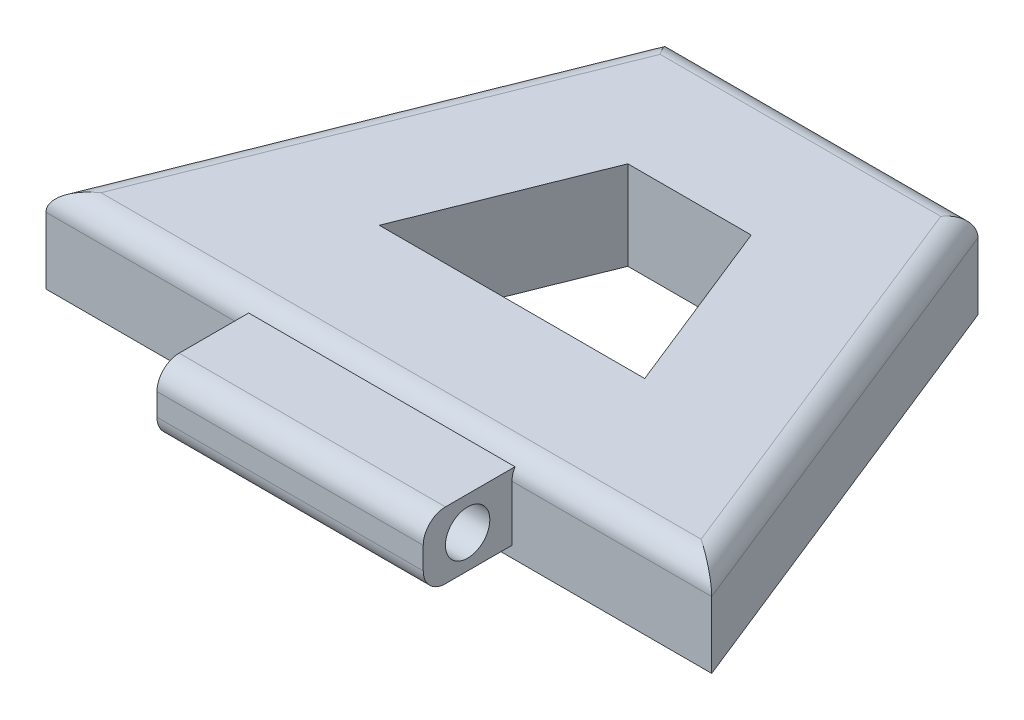
SolidWorks part; units mm, degrees
ref_plane "Front Plane" through (0, 0, 0) normal (0, 0, 1) x (1, 0, 0)
ref_plane "Top Plane" through (0, 0, 0) normal (0, 1, 0) x (1, 0, 0)
ref_plane "Right Plane" through (0, 0, 0) normal (1, 0, 0) x (0, 0, -1)
sketch "Sketch1" plane through (0, 0, 0) normal (0, 1, 0) x (1, 0, 0)
  line L0 (0, 100) -> (0, -92.25) construction
  line L1 (-140.5, 0) -> (124.5, 0) construction
  line L2 (-35, 100) -> (35, 100)
  line L3 (35, 100) -> (75, 0)
  line L4 (75, 0) -> (-75, 0)
  line L5 (-13.9, 70) -> (13.9, 70)
  line L6 (13.9, 70) -> (29.9, 30)
  line L7 (-29.9, 30) -> (29.9, 30)
  line L8 (-35, 100) -> (-75, 0)
  line L9 (-13.9, 70) -> (-29.9, 30)
  point P13 (0, 30)
  point P14 (0, 0)
  point P16 (0, 70)
  dimension "D1" = 35
  dimension "D2" = 100
  dimension "D3" = 30
  dimension "D4" = 30
  dimension "D5" = 150
extrude "Boss-Extrude1" add sketch "Sketch1" along normal blind 20
sketch "Sketch2" plane through (0, 0, 0) normal (0, 0, 1) x (1, 0, 0)
  line L0 (0, 20) -> (0, 0) construction
  line L1 (-75, 20) -> (75, 20) construction
  line L2 (-75, 10) -> (75, 10) construction
  line L3 (-75, 20) -> (-75, 0) construction
  line L4 (75, 20) -> (75, 0) construction
  line L6 (-30, 17.5) -> (30, 17.5)
  line L7 (-30, 17.5) -> (-30, 2.5)
  line L8 (-30, 2.5) -> (30, 2.5)
  line L9 (30, 17.5) -> (30, 2.5)
  line L10 (-30, 17.5) -> (30, 2.5) construction
  line L11 (-30, 2.5) -> (30, 17.5) construction
  point P11 (0, 10)
  dimension "D1" = 15
  dimension "D2" = 60
extrude "Boss-Extrude2" add sketch "Sketch2" along normal blind 20 contours L6 L9 L8 L7
sketch "Sketch3" plane through (30, 0, 0) normal (1, 0, 0) x (0, 0, -1)
  line L0 (-10, 17.5) -> (-10, 2.5) construction
  line L1 (-20, 17.5) -> (0, 17.5) construction
  line L2 (-20, 2.5) -> (0, 2.5) construction
  line L3 (-20, 10) -> (0, 10) construction
  line L4 (-20, 17.5) -> (-20, 2.5) construction
  line L5 (0, 17.5) -> (0, 2.5) construction
  circle A0 centre (-10, 10) radius 5
  dimension "D1" = 10
extrude "Cut-Extrude1" cut sketch "Sketch3" against normal through all
fillet "Fillet1" radius 5 6 edges at (0, 20, 0) (-55, 20, -50) (0, 20, -100) (55, 20, -50) (0, 2.5, 20) (0, 17.5, 20)
